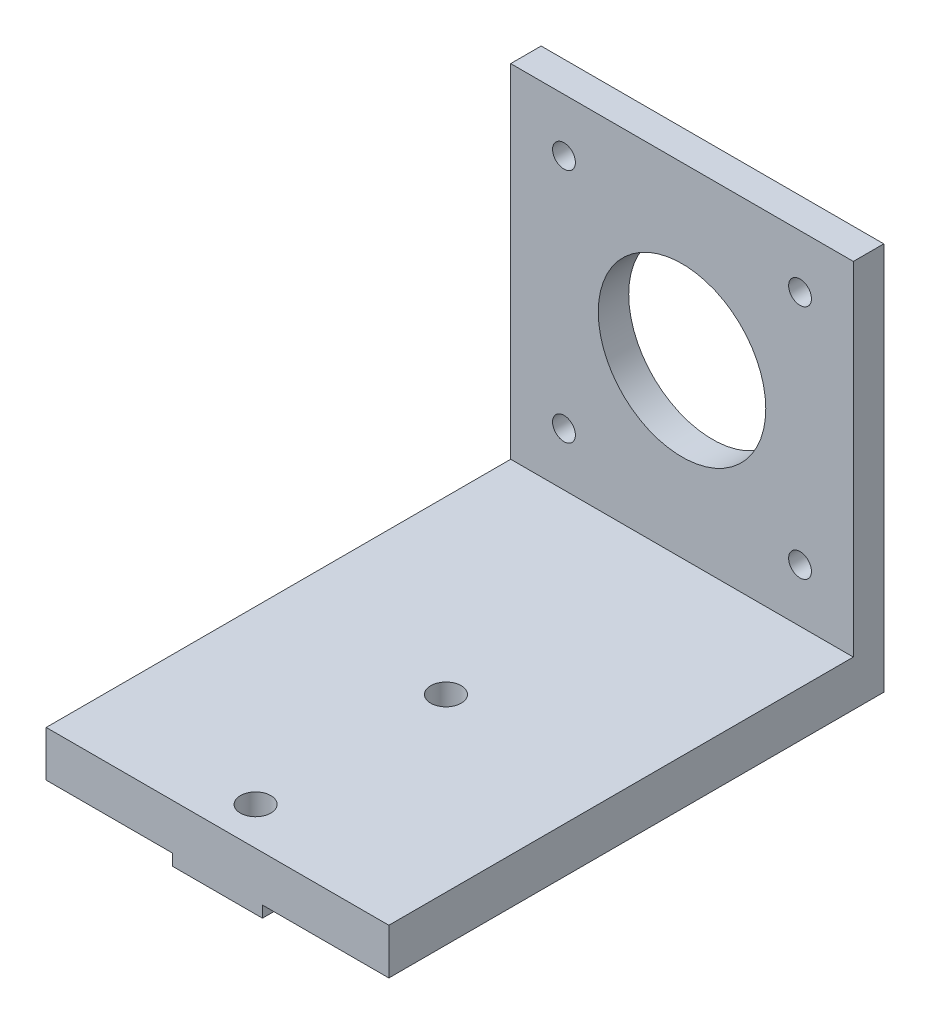
SolidWorks part; units mm, degrees
ref_plane "Front Plane" through (0, 0, 0) normal (0, 0, 1) x (1, 0, 0)
ref_plane "Top Plane" through (0, 0, 0) normal (0, 1, 0) x (1, 0, 0)
ref_plane "Right Plane" through (0, 0, 0) normal (1, 0, 0) x (0, 0, -1)
sketch "Sketch1" plane through (0, 0, 0) normal (0, 0, 1) x (1, 0, 0)
  line L0 (16.7358, 20.15) -> (-16.7358, 20.15)
  line L1 (-16.7358, 20.15) -> (-20.15, 16.7358)
  line L2 (-20.15, 16.0771) -> (-20.15, -16.7358)
  line L5 (-16.7358, -20.15) -> (16.7358, -20.15)
  line L7 (20.15, -16.7358) -> (20.15, 16.7358)
  line L8 (20.15, 16.7358) -> (16.7358, 20.15)
  line L9 (-20.15, 16.0771) -> (-20.15, 16.7358)
  line L10 (-20.15, -16.7358) -> (-20.15, -20.15)
  line L11 (-20.15, -20.15) -> (-16.7358, -20.15)
  line L12 (16.7358, -20.15) -> (20.15, -20.15)
  line L13 (20.15, -20.15) -> (20.15, -16.7358)
  line L15 (-22.5, 22.5) -> (22.5, 22.5)
  line L16 (-22.5, 22.5) -> (-22.5, -22.5)
  line L17 (-22.5, -22.5) -> (22.5, -22.5)
  line L18 (22.5, 22.5) -> (22.5, -22.5)
  circle A0 centre (-15.5, 15.5) radius 1.5
  circle A1 centre (-15.5, -15.5) radius 1.5
  circle A2 centre (15.5, 15.5) radius 1.5
  circle A3 centre (15.5, -15.5) radius 1.5
  circle A4 centre (0, 0) radius 11
  dimension "D1" = 22
  dimension "D2" = 3
  dimension "D3" = 3
  dimension "D4" = 3
  dimension "D5" = 3
  dimension "D6" = 45
  dimension "D7" = 45
  dimension "D8" = 22.5
  dimension "D9" = 22.5
extrude "Boss-Extrude1" add sketch "Sketch1" along normal blind 4 contours L18 L15 L16 L17 L13 L12 L5 L11 L10 L2 L9 L1 L0 L8 L7 | L12 L13 L7 L8 L0 L1 L9 L2 L10 L11 L5 A4 A3 A2 A1 A0 region at (18.0399, 18.0399, 0) region at (0, 21.8636, 0)
sketch "Sketch2" plane through (0, -24.1499, 0) normal (0, 1, 0) x (1, 0, 0)
  line L7 (6.0001, 199.3766) -> (6.0001, -250.6234) construction
  line L8 (5.9984, 199.3766) -> (5.9984, -250.6234) construction
  line L9 (-5.9999, 199.3766) -> (-5.9999, -250.6234) construction
  line L10 (-22.5, -4) -> (-22.5, 0) construction
  line L11 (5.9001, -65) -> (-5.8999, -65)
  line L12 (5.9001, -65) -> (5.9001, 0)
  line L13 (5.9001, 0) -> (-5.8999, 0)
  line L14 (-5.8999, -65) -> (-5.8999, 0)
  line L15 (-22.5, 0) -> (22.5, 0)
  line L16 (-22.5, 0) -> (-22.5, -65)
  line L19 (-19.4999, 0) -> (19.5, 0)
  line L21 (-22.5, -65) -> (22.5, -65)
  line L22 (22.5, 0) -> (22.5, -65)
  line L25 (-22.5, -4) -> (22.5, -4) construction
  line L26 (22.5, -4) -> (22.5, 0) construction
  circle A0 centre (0.0001, -35) radius 2
  circle A1 centre (-0.0016, -60) radius 2
  point P2 (22.5, -2)
  line M5 (19.5, -250.6234) -> (19.5, 199.3766)
  line M7 (6.3, 199.3766) -> (6.3, -250.6234)
  dimension "D3" = 4
  dimension "D4" = 4
  dimension "D2" = 35
  dimension "D5" = 25
  dimension "D6" = 0
  dimension "D7" = 6
  dimension "D8" = 6
  dimension "D9" = 0.1
  dimension "D10" = 65
  dimension "D11" = 0.1
  dimension "D12" = 0
  dimension "D13" = 0
  dimension "D14" = 4
  dimension "D15" = 0
extrude "Boss-Extrude2" add sketch "Sketch2" against normal blind 6 from surface contours L22 L15 L21 M5 | L21 L15 M7 M5 | L16 L21 L14 L15 | L12 L21 L15 M7 | L14 L11 L12 L13 A1 A0 region at (0.0001, -24.1499, 31.9918) region at (6.1001, -24.1499, 32.5) region at (-14.2, -24.1499, 32.5) region at (12.9, -24.1499, 32.5) region at (21, -24.1499, 32.5) starting at face at (0, -22.5, 2)
extrude "Boss-Extrude4" add sketch "Sketch2<5>" against normal blind 1.5 from surface contours L14 L12 A1 A0 region at (0.0001, -24.1499, 31.9918) starting at face at (0.0001, -28.5, 37)
sketch "Sketch2<5>" plane through (0, -24.1499, 0) normal (0, 1, 0) x (1, 0, 0) same geometry as "Sketch2"
